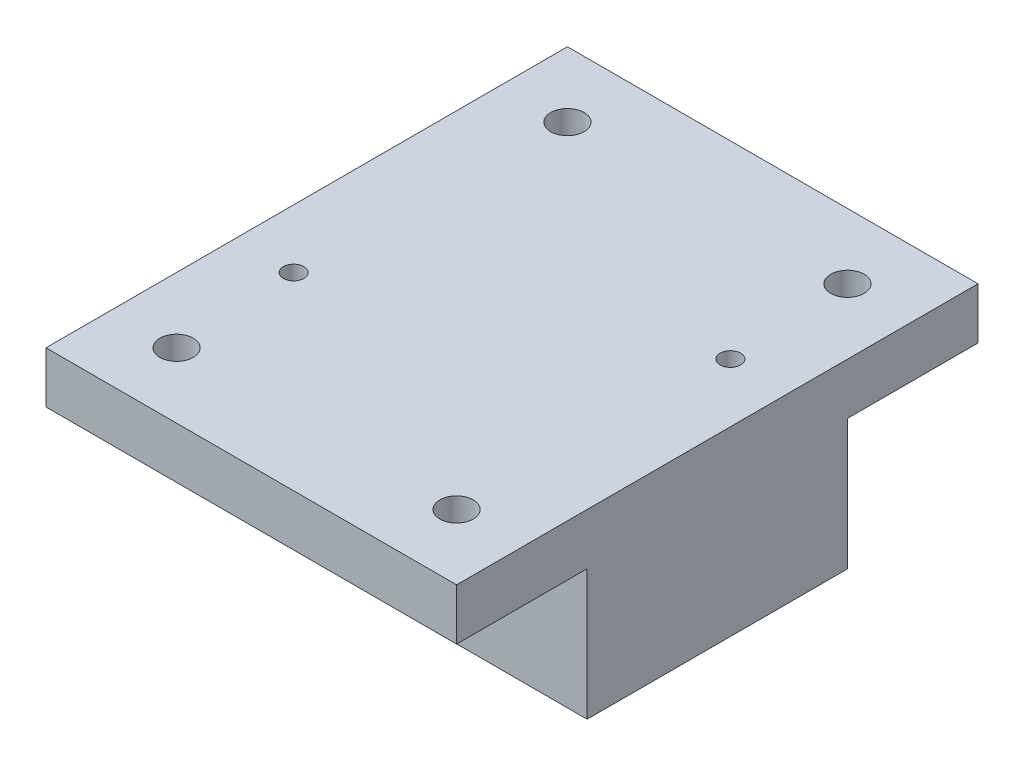
SolidWorks part; units mm, degrees
material "PETG"
ref_plane "Front Plane" through (0, 0, 0) normal (0, 0, 1) x (1, 0, 0)
ref_plane "Top Plane" through (0, 0, 0) normal (0, 1, 0) x (1, 0, 0)
ref_plane "Right Plane" through (0, 0, 0) normal (1, 0, 0) x (0, 0, -1)
sketch "Sketch1" plane through (0, 0, 0) normal (0, 1, 0) x (1, 0, 0)
  line L0 (-27.2813, 38.0813) -> (-27.2813, 50.8) construction
  line L1 (-40, -25.3625) -> (40, -25.3625)
  line L2 (-40, -25.3625) -> (-40, 25.3625)
  line L3 (-40, 25.3625) -> (40, 25.3625)
  line L4 (40, -25.3625) -> (40, 25.3625)
  line L5 (-40, 50.8) -> (40, 50.8)
  line L6 (-40, 50.8) -> (-40, -50.8)
  line L7 (-40, -50.8) -> (40, -50.8)
  line L8 (40, 50.8) -> (40, -50.8)
  line L9 (-27.2813, 38.0813) -> (-40, 38.0813) construction
  line L10 (-27.2813, 38.0813) -> (-27.2813, 25.3625) construction
  line L11 (27.2813, 38.0813) -> (40, 38.0813) construction
  line L13 (-27.2813, -38.0812) -> (-27.2813, -25.3625) construction
  circle A0 centre (-27.2813, 38.0813) radius 3.25
  circle A1 centre (27.2813, 38.0813) radius 3.25
  circle A2 centre (-27.2813, -38.0812) radius 3.25
  circle A3 centre (27.2813, -38.0812) radius 3.25
  point P4 (-40, 0)
  point P5 (0, 25.3625)
  dimension "D4" = 6.5
  dimension "D1" = 50.725
  dimension "D2" = 80
  dimension "D3" = 101.6
extrude "Boss-Extrude1" add sketch "Sketch1" along normal blind 10 contours L1 L4 L3 L2 | L8 L1 L6 L7 | L8 L5 L6 L3 region at (0, 0, 0) region at (0, 0, 38.0812) region at (0, 0, -38.0812)
extrude "Boss-Extrude2" add sketch "Sketch1<3>" against normal blind 25.4 contours L1 L4 L3 L2 region at (0, 0, 0)
sketch "Sketch1<3>" plane through (0, 0, 0) normal (0, 1, 0) x (1, 0, 0) same geometry as "Sketch1"
sketch "Sketch2" plane through (0, 10, 0) normal (0, 1, 0) x (1, 0, 0)
  line L0 (-40, 0) -> (40, 0) construction
  line L1 (-40, -50.8) -> (-40, 50.8) construction
  line L2 (40, -50.8) -> (40, 50.8) construction
  line L3 (0, 50.8) -> (0, -50.8) construction
  line L4 (-40, 50.8) -> (40, 50.8) construction
  line L5 (-40, -50.8) -> (40, -50.8) construction
  line L6 (-28.575, -13.97) -> (-28.575, 0) construction
  line L7 (-28.575, -13.97) -> (0, -13.97) construction
  line L8 (28.575, 0) -> (28.575, 13.97) construction
  line L9 (28.575, 13.97) -> (0, 13.97) construction
  circle A0 centre (-28.575, -13.97) radius 2
  circle A1 centre (28.575, 13.97) radius 2
  dimension "D2" = 4
  dimension "D1" = 13.97
  dimension "D3" = 28.575
extrude "Cut-Extrude1" cut sketch "Sketch2" against normal through all
equation "\"tol_dia_id_intfc\" = 0.0500mm ' For hole diameters - Interference fit"
equation "\"tol_dia_id_slip\"  = 0.0750mm ' For hole diameters - Slip fit"
equation "\"tol_dia_id_clear\" = 0.1000mm ' For hole diameters - Clearance fit"
equation "\"tol_dia_od_intfc\" = 0.0500mm ' For shaft diameters - Interference fit"
equation "\"tol_dia_od_slip\"  = 0.0750mm ' For shaft diameters - Slip fit"
equation "\"tol_dia_od_clear\" = 0.1000mm ' For shaft diameters - Clearance fit"
equation "\"tol_general_intfc\"= 0.0250mm ' For general parts (Horiz) - Interference fit"
equation "\"tol_general_slip\" = 0.0375mm ' For general parts (Horiz) - Slip fit"
equation "\"tol_general_clear\"= 0.0500mm ' For general parts (Horiz) - Clearance fit"
equation "\"tol_layer_intfc\"  = 0.0250mm ' For all parts (Vert) - Interference fit"
equation "\"tol_layer_slip\"   = 0.0375mm ' For all parts (Vert) - Slip fit"
equation "\"tol_layer_clear\"  = 0.0500mm ' For all parts (Vert) - Clearance fit"
equation "\"tol_corner_rad\"   = 0.100mm ' For corners that fit into other parts"
equation "\"D1@Sketch1\"=50.80mm-\"tol_general_slip\"*2"
equation "\"D2@Sketch2\"=3.95+\"tol_dia_id_intfc\""
